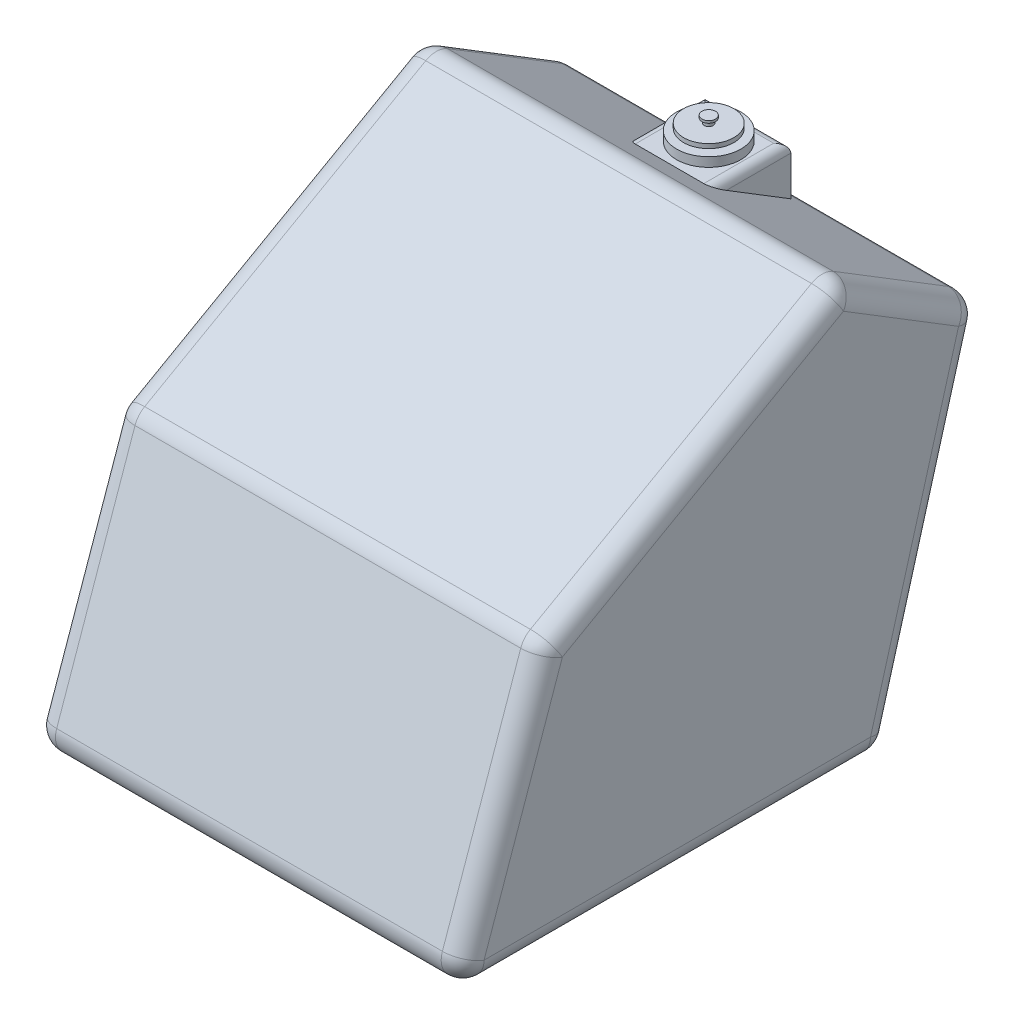
SolidWorks part; units mm, degrees
ref_plane "Front Plane" through (0, 0, 0) normal (0, 0, 1) x (1, 0, 0)
ref_plane "Top Plane" through (0, 0, 0) normal (0, 1, 0) x (1, 0, 0)
ref_plane "Right Plane" through (0, 0, 0) normal (1, 0, 0) x (0, 0, -1)
sketch "Sketch2" plane through (0, 0, 0) normal (1, 0, 0) x (0, 0, -1)
  line L0 (748.7853, 41.7029) -> (974.693, 841.7029)
  line L1 (974.693, 841.7029) -> (648.7853, 1041.7029)
  line L2 (648.7853, 1041.7029) -> (-49.0478, 646.9677)
  line L3 (-49.0478, 646.9677) -> (-261.353, 41.7029)
  line L4 (-261.353, 41.7029) -> (748.7853, 41.7029)
  point P2 (-562.9228, 827.2166)
  point P6 (629.2865, 907.9972)
  point P7 (974.693, 779.8625)
  point P8 (648.7853, 1041.7029)
  dimension "D1" = 1000
  dimension "D2" = 1010.1382
  dimension "D3" = 800
  dimension "D4" = 100
extrude "Boss-Extrude1" add sketch "Sketch2" along normal blind 1000
fillet "Fillet1" radius 50 15 edges at (500, 41.7029, -748.7853) (500, 41.7029, 261.353) (500, 646.9677, 49.0478) (500, 841.7029, -974.693) (500, 1041.7029, -648.7853) (0, 441.7029, -861.7391) (0, 941.7029, -811.7391) (0, 844.3353, -299.8687) (0, 344.3353, 155.2004) (0, 41.7029, -243.7162) (1000, 344.3353, 155.2004) (1000, 844.3353, -299.8687) (1000, 941.7029, -811.7391) (1000, 441.7029, -861.7391) (1000, 41.7029, -243.7162)
ref_plane "Plane2" through (500, 0, 0) normal (1, 0, 0) x (0, 0, -1)
sketch "Sketch5" plane through (500, 0, 0) normal (1, 0, 0) x (0, 0, -1)
  line L0 (741.9185, 984.5498) -> (924.8575, 984.5498)
  line L1 (673.9034, 1026.2886) -> (942.4441, 861.4931) construction
  line L2 (924.8575, 984.5498) -> (924.8575, 872.2855)
  line L3 (833.388, 984.5498) -> (833.388, 1258.3818) construction
  line L4 (924.8575, 984.5498) -> (908.3943, 984.5498)
  line L5 (908.3943, 984.5498) -> (908.3943, 1006.0703)
  line L6 (908.3943, 1006.0703) -> (845.2772, 1006.0703)
  line L7 (845.2772, 1006.0703) -> (845.2772, 1010.8493)
  line L8 (845.2772, 1010.8493) -> (892.0408, 1010.8493)
  line L9 (892.0408, 1010.8493) -> (892.0408, 1020.9777)
  line L10 (892.0408, 1020.9777) -> (843.5714, 1020.9777)
  line L11 (843.5714, 1020.9777) -> (843.5714, 1031.8296)
  line L12 (843.5714, 1031.8296) -> (849.2101, 1031.8296)
  line L13 (849.2101, 1031.8296) -> (849.2101, 1037.1237)
  line L14 (849.2101, 1037.1237) -> (833.388, 1037.1237)
  line L15 (833.388, 1037.1237) -> (833.388, 984.5498)
  line L16 (741.9185, 984.5498) -> (924.8575, 872.2855)
revolve "Revolve1" add sketch "Sketch5" angle 360 about L3 region at (500, 1003.3219, -865.7226)
extrude "Boss-Extrude2" add sketch "Sketch5<4>" along normal mid plane 200 contours L0 L16 L2 region at (500, 947.1283, -863.8778)
sketch "Sketch5<4>" plane through (500, 0, 0) normal (1, 0, 0) x (0, 0, -1) same geometry as "Sketch5"
fillet "Fillet2" radius 20 3 edges at (400, 984.5498, -833.388) (500, 984.5498, -924.8575) (600, 984.5498, -833.388)
